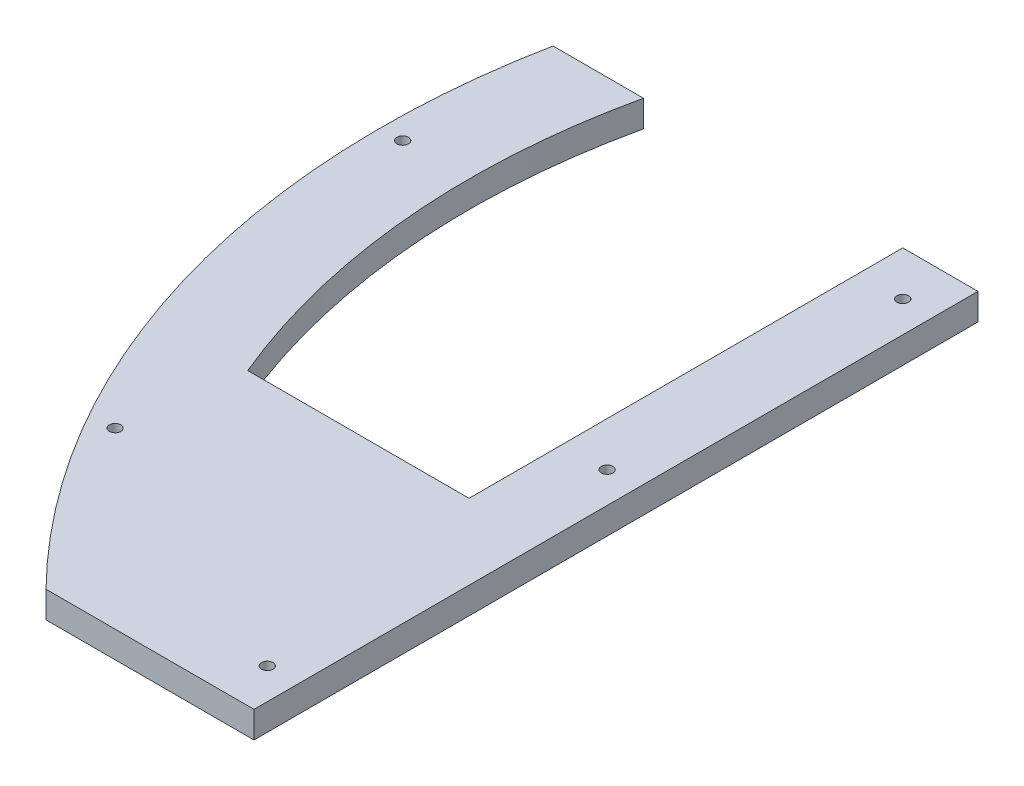
SolidWorks part; units mm, degrees
ref_plane "Front Plane" through (0, 0, 0) normal (0, 0, 1) x (1, 0, 0)
ref_plane "Top Plane" through (0, 0, 0) normal (0, 1, 0) x (1, 0, 0)
ref_plane "Right Plane" through (0, 0, 0) normal (1, 0, 0) x (0, 0, -1)
sketch "Sketch1" plane through (0, 0, 0) normal (0, 1, 0) x (1, 0, 0)
  line L0 (0, 0) -> (0, -162.5) construction
  line L2 (-100, -144.5) -> (100, -144.5)
  line L3 (-100, -144.5) -> (-100, 35.5)
  line L4 (-100, 35.5) -> (100, 35.5)
  line L5 (100, -144.5) -> (100, 35.5)
  line L6 (-100, -144.5) -> (100, 35.5) construction
  line L7 (-100, 35.5) -> (100, -144.5) construction
  circle A0 centre (0, 0) radius 162.5
  point P4 (0, -54.5)
  dimension "D1" = 325
  dimension "D2" = 180
  dimension "D3" = 35.5
  dimension "D4" = 200
sketch "Sketch2" plane through (0, 0, 0) normal (0, 1, 0) x (1, 0, 0)
  line L0 (-100, -144.5) -> (-100, 35.5) construction
  line L1 (-100, 35.5) -> (100, 35.5) construction
  line L2 (100, -144.5) -> (100, 35.5) construction
  line L3 (-100, -128.0869) -> (-100, 35.5)
  line L4 (-100, 35.5) -> (100, 35.5)
  line L5 (100, -128.0869) -> (100, 35.5)
  circle A0 centre (0, 0) radius 162.5 construction
  arc A1 (100, -128.0869) -> (-100, -128.0869) centre (0, 0) ccw
extrude "Boss-Extrude1" add sketch "Sketch2" along normal blind 6
sketch "Sketch4" plane through (0, 6, 0) normal (0, 1, 0) x (1, 0, 0)
  line L0 (0, 0) -> (0, 162.5) construction
  line L1 (119.15, -101.1581) -> (123.8764, -105.1708) construction
  line L2 (100, 35.5) -> (100, -128.0869) construction
  line L4 (-100, 35.5) -> (100, 35.5) construction
  arc A0 (100, -128.0869) -> (-100, -128.0869) centre (0, 0) ccw construction
  circle A1 centre (119.15, -101.1581) radius 1
  circle A2 centre (87.75, 86.5) radius 1
  circle A3 centre (152, 23.5891) radius 1
  circle A4 centre (-87.75, 86.5) radius 1
  circle A5 centre (99, 36.6) radius 1
  circle A6 centre (-99, 36.6) radius 1
  circle A7 centre (-152, 23.5891) radius 1
  circle A8 centre (-119.15, -101.1581) radius 1
  dimension "D1" = 2
  dimension "D3" = 6.2
  dimension "D2" = 129
  dimension "D4" = 19.15
  dimension "D5" = 52
  dimension "D6" = 51
  dimension "D7" = 87.75
  dimension "D8" = 1.1
extrude "Cut-Extrude2" [suppressed] cut sketch "Sketch4" against normal through all
sketch "Sketch5" plane through (0, 6, 0) normal (0, 1, 0) x (1, 0, 0)
  line L0 (-100, -128.0869) -> (-100, 35.5) construction
  line L1 (-100, -108.0869) -> (100, -108.0869)
  line L2 (-100, -108.0869) -> (-100, -128.0869)
  line L3 (-100, -128.0869) -> (100, -128.0869)
  line L4 (100, -108.0869) -> (100, -128.0869)
  dimension "D1" = 20
extrude "Boss-Extrude2" add sketch "Sketch5" against normal blind 6
sketch "Sketch6" plane through (0, 6, 0) normal (0, 1, 0) x (1, 0, 0)
  line L0 (0, 0) -> (0, -108.0869) construction
  line L1 (100, -108.0869) -> (-100, -108.0869) construction
  line L2 (-100, 35.5) -> (100, 35.5) construction
  line L4 (-13.5, -108.0869) -> (-13.5, 35.5)
  line L5 (-13.5, -108.0869) -> (-100, -108.0869)
  line L6 (13.5, -108.0869) -> (13.5, 35.5)
  line L7 (-13.5, -108.0869) -> (13.5, 35.5) construction
  line L8 (-13.5, 35.5) -> (13.5, -108.0869) construction
  line L9 (-100, -108.0869) -> (-100, 35.5) construction
  line L10 (-100, -108.0869) -> (-100, 35.5)
  line L11 (100, -108.0869) -> (13.5, -108.0869)
  line L12 (-13.5, 35.5) -> (-100, 35.5)
  line L13 (-100, -108.0869) -> (100, -108.0869)
  line L14 (-100, 35.5) -> (-100, -108.0869)
  line L15 (100, 35.5) -> (-100, 35.5)
  line L16 (100, -108.0869) -> (100, 35.5)
  line L17 (-100, -108.0869) -> (-13.5, -108.0869)
  line L18 (-100, 35.5) -> (-100, -108.0869)
  line L19 (100, 35.5) -> (13.5, 35.5)
  line L20 (100, -108.0869) -> (100, 35.5)
  line L21 (13.5, -108.0869) -> (100, -108.0869)
  point P5 (0, -36.2934)
  line M5 (100, -108.0869) -> (-100, -108.0869)
  line M6 (-100, -108.0869) -> (-100, 35.5)
  line M7 (-100, 35.5) -> (100, 35.5)
  line M8 (100, 35.5) -> (100, -108.0869)
  dimension "D1" = 27
  dimension "D2" = 0
extrude "Boss-Extrude3" add sketch "Sketch6" against normal through all contours L4 M5 M7 M6 | L6 M5 M8 M7 region at (-56.75, 6, 36.2934) region at (56.75, 6, 36.2934)
sketch "Sketch7" plane through (0, 6, 0) normal (0, 1, 0) x (1, 0, 0)
  line L0 (-150, -62.5) -> (-100, -62.5)
  line L1 (-100, -144.5) -> (-100, 35.5) construction
  line L2 (-158.5749, 35.5) -> (-100, 35.5)
  line L3 (-100, 35.5) -> (-100, -62.5)
  line L4 (0, 0) -> (0, -162.5) construction
  line L5 (100, 35.5) -> (100, -62.5)
  line L6 (158.5749, 35.5) -> (100, 35.5)
  line L7 (150, -62.5) -> (100, -62.5)
  line L8 (-100, 35.5) -> (100, 35.5) construction
  arc A0 (100, -128.0869) -> (-100, -128.0869) centre (0, 0) ccw construction
  circle A1 centre (0, 0) radius 162.5 construction
  arc A2 (-158.5749, 35.5) -> (-150, -62.5) centre (0, 0) ccw
  arc A3 (158.5749, 35.5) -> (150, -62.5) centre (0, 0) cw
  dimension "D1" = 50
extrude "Cut-Extrude3" cut sketch "Sketch7" against normal through all
sketch "Sketch8" plane through (0, 6, 0) normal (0, 1, 0) x (1, 0, 0)
  line L0 (0, 162.5) -> (0, 0) construction
  line L1 (-30, 132.5) -> (-30, 159.7068)
  line L2 (30, 132.5) -> (30, 159.7068)
  arc A0 (-30, 132.5) -> (30, 132.5) centre (0, 132.5) ccw
  circle A1 centre (0, 0) radius 162.5 construction
  arc A2 (30, 159.7068) -> (-30, 159.7068) centre (0, 0) ccw
  dimension "D1" = 60
extrude "Cut-Extrude4" cut sketch "Sketch8" against normal through all
sketch "Sketch9" plane through (0, 6, 0) normal (0, 1, 0) x (1, 0, 0)
  line L0 (0, 0) -> (0, 162.5) construction
  line L1 (-105, 107) -> (105, 107)
  line L2 (-105, 107) -> (-105, 55)
  line L3 (-105, 55) -> (105, 55)
  line L4 (105, 107) -> (105, 55)
  line L5 (-105, 107) -> (105, 55) construction
  line L6 (-105, 55) -> (105, 107) construction
  line L7 (-100, 35.5) -> (100, 35.5) construction
  circle A0 centre (0, 0) radius 162.5 construction
  point P0 (0, 81)
  dimension "D1" = 52
  dimension "D2" = 210
  dimension "D3" = 19.5
extrude "Cut-Extrude5" cut sketch "Sketch9" against normal through all
sketch "Sketch10" plane through (0, 6, 0) normal (0, 1, 0) x (1, 0, 0)
  line L0 (-100, -128.0869) -> (-130, -128.0869)
  line L1 (100, -128.0869) -> (130, -128.0869)
  arc A0 (130, -128.0869) -> (-130, -128.0869) centre (0, 0) ccw
  circle A1 centre (0, 0) radius 162.5 construction
  arc A2 (100, -128.0869) -> (-100, -128.0869) centre (0, 0) ccw
  dimension "D1" = 20
extrude "Boss-Extrude4" add sketch "Sketch10" against normal through all
fillet "Fillet1" radius 10 4 edges at (105, 3, -107) (105, 3, -55) (-105, 3, -55) (-105, 3, -107)
sketch "Sketch11" plane through (0, 6, 0) normal (0, 1, 0) x (1, 0, 0)
  line L0 (0, 182.5) -> (0, 162.5) construction
  arc A1 (130, -128.0869) -> (-130, -128.0869) centre (0, 0) ccw construction
  arc A2 (30, 159.7068) -> (-30, 159.7068) centre (0, 0) ccw construction
  circle A3 centre (0, 177.5) radius 1.3
  circle A4 centre (88.75, 153.7195) radius 1.3
  circle A5 centre (153.7195, 88.75) radius 1.3
  circle A6 centre (177.5, 0) radius 1.3
  circle A7 centre (153.7195, -88.75) radius 1.3
  circle A8 centre (88.75, -153.7195) radius 1.3
  circle A9 centre (0, -177.5) radius 1.3
  circle A10 centre (-88.75, -153.7195) radius 1.3
  circle A11 centre (-153.7195, -88.75) radius 1.3
  circle A12 centre (-177.5, 0) radius 1.3
  circle A13 centre (-153.7195, 88.75) radius 1.3
  circle A14 centre (-88.75, 153.7195) radius 1.3
  point P36 (0, 0)
  dimension "D1" = 2.6
  dimension "D3" = 5
  dimension "D2" = 12
extrude "Cut-Extrude6" cut sketch "Sketch11" against normal through all
sketch "Sketch12" plane through (0, 6, 0) normal (0, 1, 0) x (1, 0, 0)
  line L0 (-139.1465, -118.0869) -> (139.1465, -118.0869) construction
  line L1 (-130, -128.0869) -> (130, -128.0869) construction
  line L2 (-100, -144.5) -> (-100, 35.5) construction
  line L3 (100, -144.5) -> (100, 35.5) construction
  line L4 (-90, -118.0869) -> (-90, 35.5) construction
  line L5 (0, 0) -> (0, -118.0869) construction
  line L6 (-100, 35.5) -> (100, 35.5) construction
  arc A0 (130, -128.0869) -> (-130, -128.0869) centre (0, 0) ccw construction
  circle A1 centre (0, -118.0869) radius 1.3
  circle A2 centre (-90, -118.0869) radius 1.3
  circle A3 centre (90, -118.0869) radius 1.3
  circle A4 centre (-90, 25.5) radius 1.3
  circle A5 centre (-90, -41.2934) radius 1.3
  circle A6 centre (90, -41.2934) radius 1.3
  circle A7 centre (90, 25.5) radius 1.3
  dimension "D2" = 2.6
  dimension "D1" = 10
  dimension "D3" = 10
  dimension "D4" = 10
  dimension "D5" = 10
extrude "Cut-Extrude7" cut sketch "Sketch12" against normal through all
sketch "Sketch13" plane through (0, 6, 0) normal (0, 1, 0) x (1, 0, 0)
  line L0 (0, 0) -> (0, 35.5) construction
  line L1 (-13.5, 35.5) -> (13.5, 35.5) construction
  circle A0 centre (-17.875, -13.5) radius 1.75
  circle A1 centre (17.875, -13.5) radius 1.75
  dimension "D3" = 3.5
  dimension "D1" = 35.75
  dimension "D2" = 13.5
extrude "Cut-Extrude8" cut sketch "Sketch13" against normal blind 10
sketch "Sketch14" plane through (0, 6, 0) normal (0, 1, 0) x (1, 0, 0)
  line L0 (-15.8035, 107) -> (-95, 107) construction
  line L1 (0, 0) -> (0, 162.5) construction
  line L2 (-30, 132.5) -> (30, 132.5)
  line L3 (55.5, 107) -> (-55.5, 107)
  line L4 (-30, 159.7068) -> (-30, 132.5) construction
  arc A0 (-30, 132.5) -> (-55.5, 107) centre (-55.5, 132.5) cw
  arc A1 (30, 159.7068) -> (-30, 159.7068) centre (0, 0) ccw construction
  arc A2 (30, 132.5) -> (55.5, 107) centre (55.5, 132.5) ccw
extrude "Cut-Extrude9" cut sketch "Sketch14" against normal through all
sketch "Sketch15" plane through (0, 6, 0) normal (0, 1, 0) x (1, 0, 0)
  line L0 (-95, 55) -> (-174.0151, 55)
  line L1 (-83, 55) -> (-83, -128.0869)
  line L2 (-95, 55) -> (95, 55) construction
  line L3 (-130, -128.0869) -> (130, -128.0869) construction
  line L4 (-130, -128.0869) -> (-83, -128.0869)
  line L5 (-95, 55) -> (-83, 55)
  arc A0 (130, -128.0869) -> (-130, -128.0869) centre (0, 0) ccw construction
  arc A1 (-174.0151, 55) -> (-130, -128.0869) centre (0, 0) ccw
  circle A2 centre (0, 0) radius 208.6527
  dimension "D1" = 12
extrude "Cut-Extrude10" cut sketch "Sketch15" against normal through all
sketch "Sketch16" [suppressed] plane through (0, 0, 0) normal (0, -1, 0) x (1, 0, 0)
  line L0 (-105, -97) -> (-105, -136.8622)
  line L1 (105, -97) -> (105, -136.8622)
  line L2 (0, -55) -> (0, -162.5) construction
  line L3 (-95, -55) -> (95, -55) construction
  line L4 (-105, -97) -> (105, -97)
  arc A0 (-105, -136.8622) -> (105, -136.8622) centre (0, 0) ccw
  arc A1 (-30, -159.7068) -> (30, -159.7068) centre (0, 0) ccw construction
  arc A3 (-130, 128.0869) -> (130, 128.0869) centre (0, 0) ccw construction
  point P20 (0, -172.5)
  point P21 (0, -182.5)
  dimension "D1" = 10
extrude "Cut-Extrude11" [suppressed] cut sketch "Sketch16" against normal through all
fillet "Fillet2" [suppressed] radius 30
sketch "Sketch17" plane through (0, 6, 0) normal (0, 1, 0) x (1, 0, 0)
  line L0 (-158.5749, 35.5) -> (-179.014, 35.5)
  line L1 (-179.014, 35.5) -> (-177.4443, 58.8715)
  line L2 (-177.4443, 58.8715) -> (-77.4613, 58.8715)
  line L3 (-77.4613, 58.8715) -> (-77.4613, 35.5)
  line L4 (-77.4613, 35.5) -> (-100, 35.5)
  line L5 (-158.5749, 35.5) -> (-100, 35.5)
  arc A0 (-174.0151, 55) -> (-130, -128.0869) centre (0, 0) ccw construction
extrude "Cut-Extrude12" cut sketch "Sketch17" against normal through all
